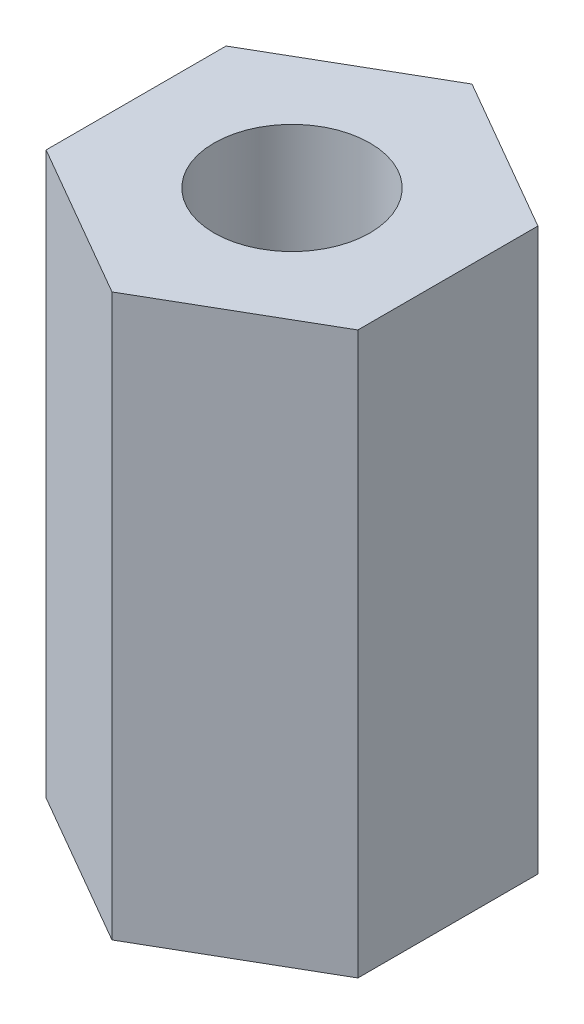
SolidWorks part; units mm, degrees
material "Nylon 101"
ref_plane "Front Plane" through (0, 0, 0) normal (0, 0, 1) x (1, 0, 0)
ref_plane "Top Plane" through (0, 0, 0) normal (0, 1, 0) x (1, 0, 0)
ref_plane "Right Plane" through (0, 0, 0) normal (1, 0, 0) x (0, 0, -1)
sketch "Sketch1" plane through (0, 0, 0) normal (0, 1, 0) x (1, 0, 0)
  line L1 (2.5, -1.4434) -> (2.5, 1.4434)
  line L2 (2.5, 1.4434) -> (0, 2.8868)
  line L3 (0, 2.8868) -> (-2.5, 1.4434)
  line L4 (-2.5, 1.4434) -> (-2.5, -1.4434)
  line L5 (-2.5, -1.4434) -> (0, -2.8868)
  line L6 (0, -2.8868) -> (2.5, -1.4434)
  circle A1 centre (0, 0) radius 2.5 construction
  dimension "D1" = 5
extrude "Boss-Extrude1" add sketch "Sketch1" along normal blind 9
ref_axis "Axis1" through (0, -0.45, 0) along (0, 1, 0)
hole_wizard "Tap Drill for M3x0.5 Tap1" positions "Sketch4" profile "Sketch5" hole size "M3x0.5" standard "ANSI Metric" end condition through all
sketch "Sketch4" plane through (0, 9, 0) normal (0, 1, 0) x (1, 0, 0)
  point P0 (0, 0)
sketch "Sketch5" plane through (0, 9, 0) normal (1, 0, 0) x (0, 0, 1)
  line L0 (0, 0) -> (0, 9)
  line L1 (0, 9) -> (1.25, 9)
  line L2 (1.25, 9) -> (1.25, 0)
  line L5 (1.25, 0) -> (0, 0)
  line L11 (0, -6.35) -> (0, 107.95) construction
  dimension "Thru Hole Dia." = 2.5
  dimension "Thru Hole Depth" = 9
